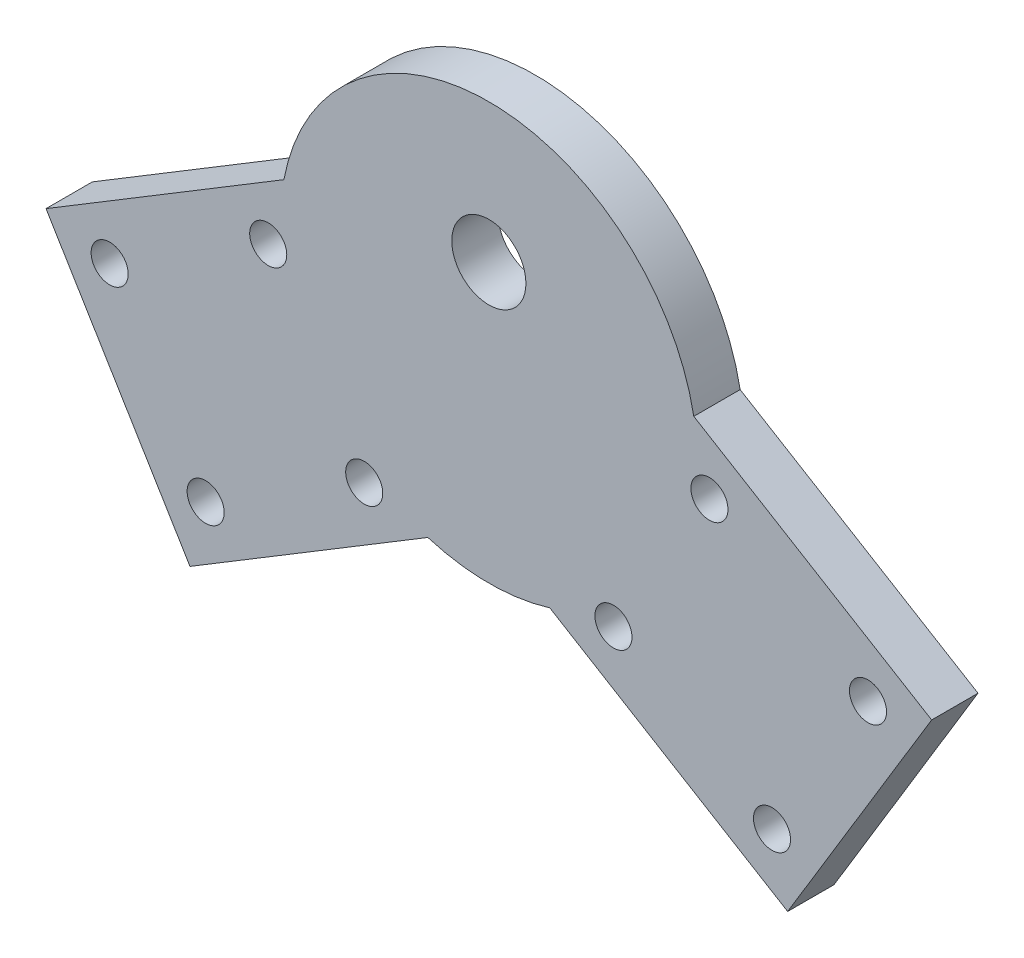
SolidWorks part; units mm, degrees
ref_plane "Front Plane" through (0, 0, 0) normal (0, 0, 1) x (1, 0, 0)
ref_plane "Top Plane" through (0, 0, 0) normal (0, 1, 0) x (1, 0, 0)
ref_plane "Right Plane" through (0, 0, 0) normal (1, 0, 0) x (0, 0, -1)
sketch "Sketch2" plane through (0, 0, 0) normal (0, 0, 1) x (1, 0, 0)
  line L8 (0, 0) -> (0, -22.5) construction
  line L9 (0, 0) -> (6.5784, -21.5169)
  line L10 (0, 0) -> (-6.5784, -21.5169)
  line L11 (6.5784, -21.5169) -> (22.1146, 4.1469)
  line L12 (6.5784, -21.5169) -> (32.2421, -37.053)
  line L13 (22.1146, 4.1469) -> (47.7783, -11.3893)
  line L14 (32.2421, -37.053) -> (47.7783, -11.3893)
  line L15 (-6.5784, -21.5169) -> (-22.1146, 4.1469)
  line L16 (-6.5784, -21.5169) -> (-32.2421, -37.053)
  line L17 (-22.1146, 4.1469) -> (-47.7783, -11.3893)
  line L18 (-32.2421, -37.053) -> (-47.7783, -11.3893)
  circle A0 centre (0, 0) radius 22.5
  dimension "D5" = 45
  dimension "D1" = 17
  dimension "D2" = 17
  dimension "D3" = 30
  dimension "D4" = 30
  dimension "D6" = 30
  dimension "D7" = 30
extrude "Boss-Extrude1" add sketch "Sketch2" along normal blind 5 contours A0 | L15 L16 L18 L17 | L11 L12 L14 L13
sketch "Sketch4" plane through (0, 0, 5) normal (0, 0, 1) x (1, 0, 0)
  line L0 (-22.1146, 4.1469) -> (-6.5784, -21.5169)
  line L1 (-22.1146, 4.1469) -> (-47.7783, -11.3893) construction
  line L2 (-6.5784, -21.5169) -> (-32.2421, -37.053) construction
  line L3 (-32.2421, -37.053) -> (-47.7783, -11.3893) construction
  line L4 (6.5784, -21.5169) -> (22.1146, 4.1469)
  line L7 (6.5784, -21.5169) -> (32.2421, -37.053) construction
  line L8 (22.1146, 4.1469) -> (47.7783, -11.3893) construction
  line L9 (32.2421, -37.053) -> (47.7783, -11.3893) construction
  circle A0 centre (-40.9116, -13.0772) radius 2
  circle A1 centre (-23.8025, -2.7198) radius 2
  circle A2 centre (-13.445, -19.8289) radius 2
  circle A3 centre (-30.5542, -30.1864) radius 2
  circle A4 centre (23.8025, -2.7198) radius 2
  circle A6 centre (13.445, -19.8289) radius 2
  circle A7 centre (40.9116, -13.0772) radius 2
  circle A8 centre (30.5542, -30.1864) radius 2
  dimension "D10" = 4
  dimension "D11" = 4
  dimension "D12" = 4
  dimension "D13" = 4
  dimension "D19" = 4
  dimension "D20" = 4
  dimension "D25" = 4
  dimension "D26" = 4
  dimension "D1" = 30
  dimension "D2" = 5
  dimension "D3" = 5
  dimension "D4" = 5
  dimension "D5" = 5
  dimension "D6" = 5
  dimension "D7" = 5
  dimension "D8" = 5
  dimension "D9" = 5
  dimension "D14" = 30
  dimension "D15" = 5
  dimension "D16" = 5
  dimension "D17" = 5
  dimension "D18" = 5
  dimension "D21" = 5
  dimension "D22" = 5
  dimension "D23" = 5
  dimension "D24" = 5
extrude "Cut-Extrude1" cut sketch "Sketch4" against normal blind 10 contours A0 | A1 | A2 | A3 | A6 | A4 | A7 | A8
sketch "Sketch5" plane through (0, 0, 5) normal (0, 0, 1) x (1, 0, 0)
  line L0 (0, 22.5) -> (0, -22.5)
  arc A0 (22.1146, 4.1469) -> (-22.1146, 4.1469) centre (0, 0) ccw construction
  arc A1 (-6.5784, -21.5169) -> (6.5784, -21.5169) centre (0, 0) ccw construction
  circle A2 centre (0, 7.5) radius 4
  point P10 (0, 0)
  point P11 (0, 0)
  dimension "D2" = 8
  dimension "D1" = 30
extrude "Cut-Extrude2" cut sketch "Sketch5" against normal blind 10 contours A2
